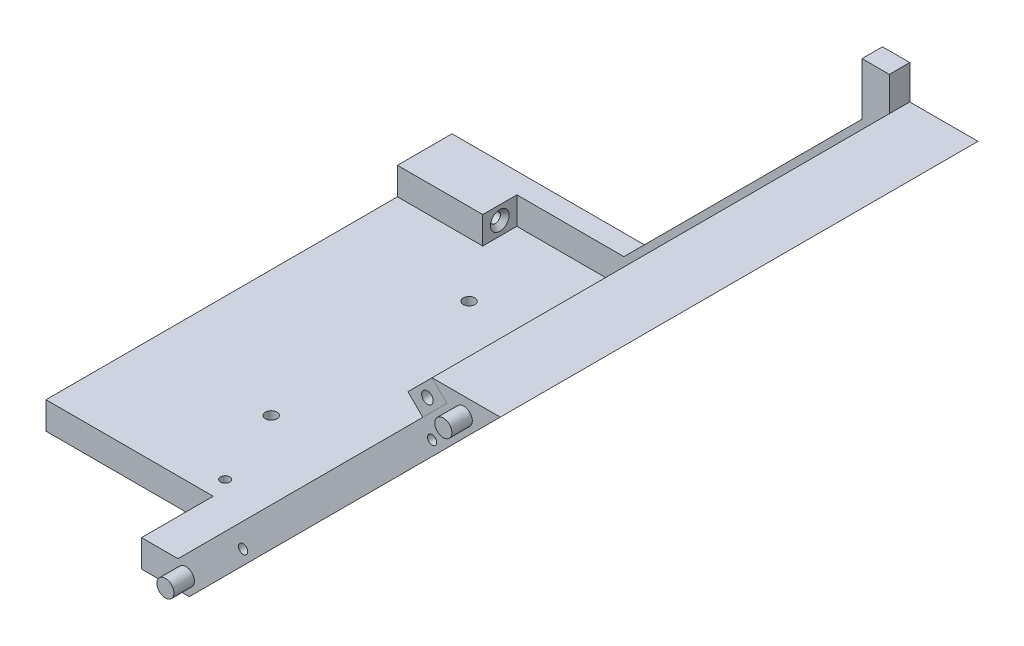
SolidWorks part; units mm, degrees
ref_plane "Plan de face" through (0, 0, 0) normal (0, 0, 1) x (1, 0, 0)
ref_plane "Plan de dessus" through (0, 0, 0) normal (0, 1, 0) x (1, 0, 0)
ref_plane "Plan de droite" through (0, 0, 0) normal (1, 0, 0) x (0, 0, -1)
sketch "Main-Sketch" plane through (0, 0, 0) normal (0, 0, 1) x (1, 0, 0)
  line L0 (0, 0) -> (63, 0)
  line L1 (63, 0) -> (154.15, 91.15)
  line L2 (154.15, 91.15) -> (134.15, 91.15)
  line L3 (134.15, 91.15) -> (138.4931, 86.8069)
  line L4 (138.4931, 86.8069) -> (59.6863, 8)
  line L5 (59.6863, 8) -> (0, 8)
  line L6 (0, 8) -> (0, 0)
  dimension "D1" = 8
  dimension "D2" = 8
  dimension "D3" = 20
  dimension "D4" = 135
  dimension "D5" = 154.15
  dimension "D6" = 63
extrude "Main-Extrusion" add sketch "Main-Sketch" along normal blind 140
sketch "Lcd-Hole-Sketch" plane through (0, 8, 0) normal (0, 1, 0) x (-1, 0, 0)
  line L1 (0, 140) -> (-49, 140)
  line L2 (0, 140) -> (0, 119)
  line L3 (0, 119) -> (-49, 119)
  line L4 (-49, 140) -> (-49, 119)
  dimension "D1" = 21
  dimension "D2" = 49
extrude "Lcd-Hole" cut sketch "Lcd-Hole-Sketch" against normal through all
sketch "Lcd-Fix-Sketch" plane through (0, 8, 0) normal (0, 1, 0) x (1, 0, 0)
  line L1 (49, -119) -> (0, -119) construction
  line L2 (49, -140) -> (49, -119) construction
  circle A0 centre (46.5, -113) radius 1.35
  dimension "D1" = 2.7
  dimension "D2" = 2.5
  dimension "D3" = 6
extrude "Lcd-Fix" cut sketch "Lcd-Fix-Sketch" against normal blind 7
sketch "Bottom-Reinforcement-Sketch" plane through (0, 0, 0) normal (0, 0, 1) x (1, 0, 0)
  line L0 (59.6863, 8) -> (138.4931, 86.8069)
  line L1 (134.15, 101.15) -> (126.15, 101.15)
  line L2 (126.15, 101.15) -> (126.15, 85.7774)
  line L5 (138.4931, 86.8069) -> (59.6863, 8) construction
  line L6 (134.15, 91.15) -> (134.15, 101.15)
  line L7 (59.6863, 8) -> (0, 8)
  line L8 (0, 0) -> (0, 8) construction
  line L9 (0, 8) -> (0, 16)
  line L10 (0, 16) -> (56.3726, 16)
  line L11 (56.3726, 16) -> (126.15, 85.7774)
  line L13 (138.4931, 86.8069) -> (134.15, 91.15)
  dimension "D1" = 8
  dimension "D2" = 10
  dimension "D3" = 8
  dimension "D4" = 8
extrude "Bottom-Reinforcement-Extrusion" add sketch "Bottom-Reinforcement-Sketch" along normal blind 6 separate body
sketch "Power-Board-Hole-Sketch" plane through (22.4244, -40.5756, 188.8128) normal (0.7071, -0.7071, 0) x (0, 0, -1)
  line L1 (150.8128, 154.2882) -> (68.8128, 154.2882)
  line L2 (150.8128, 154.2882) -> (150.8128, 80.3826)
  line L3 (150.8128, 80.3826) -> (68.8128, 80.3826)
  line L4 (68.8128, 154.2882) -> (68.8128, 80.3826)
  line L6 (188.8128, 57.3826) -> (188.8128, 186.2882) construction
  line L7 (48.8128, 57.3826) -> (48.8128, 186.2882) construction
  line L8 (48.8128, 57.3826) -> (188.8128, 57.3826) construction
  line L9 (48.8128, 186.2882) -> (188.8128, 186.2882) construction
  dimension "D1" = 20
  dimension "D2" = 38
  dimension "D3" = 32
  dimension "D4" = 23
extrude "Power-Board-Hole" cut sketch "Power-Board-Hole-Sketch" against normal through all
sketch "Power-Board-Window-Sketch" plane through (22.4244, -40.5756, 188.8128) normal (0.7071, -0.7071, 0) x (0, 0, -1)
  line L0 (150.8128, 80.3826) -> (150.8128, 154.2882) construction
  line L1 (156.8128, 160.2882) -> (62.8128, 160.2882)
  line L2 (156.8128, 160.2882) -> (156.8128, 74.3826)
  line L3 (156.8128, 74.3826) -> (62.8128, 74.3826)
  line L4 (62.8128, 160.2882) -> (62.8128, 74.3826)
  line L5 (150.8128, 154.2882) -> (68.8128, 154.2882) construction
  line L6 (68.8128, 154.2882) -> (68.8128, 80.3826) construction
  line L7 (68.8128, 80.3826) -> (150.8128, 80.3826) construction
  dimension "D1" = 6
  dimension "D2" = 6
  dimension "D3" = 6
  dimension "D4" = 6
extrude "Power-Board-Window" cut sketch "Power-Board-Window-Sketch" against normal blind 5
sketch " Power-Board-Window-Fix-Sketch" plane through (27.9645, -27.9645, 0) normal (0.7071, -0.7071, 0) x (0, 0, -1)
  line L0 (-38, 67.5477) -> (-38, 141.4533) construction
  line L1 (-38, 141.4533) -> (-120, 141.4533) construction
  line L2 (-120, 67.5477) -> (-38, 67.5477) construction
  line L3 (-120, 141.4533) -> (-120, 67.5477) construction
  circle A0 centre (-123, 104.5005) radius 1.35
  circle A1 centre (-35, 104.5005) radius 1.35
  circle A2 centre (-79, 144.4533) radius 1.35
  circle A3 centre (-79, 64.5477) radius 1.35
  point P11 (-38, 104.5005)
  point P15 (-79, 141.4533)
  point P19 (-79, 67.5477)
  point P22 (-120, 104.5005)
  dimension "D1" = 2.7
  dimension "D2" = 3
  dimension "D3" = 3
  dimension "D4" = 3
  dimension "D5" = 3
extrude "Power-Board-Window-Fix" cut sketch " Power-Board-Window-Fix-Sketch" against normal through all
sketch "PowerBoard-Fix-Sketch" plane through (25.8431, -25.8431, 0) normal (-0.7071, 0.7071, 0) x (0, 0, 1)
  line L0 (140, 159.3112) -> (0, 159.3112) construction
  line L2 (6, 47.8614) -> (6, 159.3112) construction
  circle A0 centre (13, 137.3112) radius 4
  circle A1 centre (11, 68.3112) radius 4
  dimension "D1" = 8
  dimension "D2" = 8
  dimension "D3" = 22
  dimension "D4" = 69
  dimension "D5" = 7
  dimension "D6" = 5
extrude "PowerBoard-Fix-Extrusion" add sketch "PowerBoard-Fix-Sketch" along normal blind 5
sketch "PowerBoard-Fix-Hole-Sketch" plane through (22.3076, -22.3076, 0) normal (-0.7071, 0.7071, 0) x (0, 0, 1)
  circle A0 centre (13, 137.3112) radius 1.35
  circle A1 centre (11, 68.3112) radius 1.35
  dimension "D1" = 2.7
extrude "PowerBoard-Fix-Hole" cut sketch "PowerBoard-Fix-Hole-Sketch" against normal through all
sketch "Top-Fix-Sketch" plane through (0, 0, 140) normal (0, 0, 1) x (1, 0, 0)
  line L0 (63, 0) -> (154.15, 91.15) construction
  line L1 (49, 0) -> (49, 8) construction
  line L2 (134.15, 91.15) -> (138.4931, 86.8069) construction
  circle A0 centre (62, 4.6569) radius 2.5
  circle A1 centre (143.4462, 86.0965) radius 2.5
  point P12 (49, 4)
  dimension "D1" = 5
  dimension "D2" = 5
  dimension "D4" = 4
  dimension "D5" = 3.9954
  dimension "D6" = 13
  dimension "D7" = 3
extrude "Top-Fix" add sketch "Top-Fix-Sketch" along normal blind 6
sketch "Top-Fix-Hole-Sketch" plane through (0, 0, 140) normal (0, 0, 1) x (1, 0, 0)
  line L0 (63, 0) -> (154.15, 91.15) construction
  circle A0 centre (78.7574, 20) radius 1.35
  circle A1 centre (134.15, 75.3926) radius 1.35
  dimension "D1" = 2.7
  dimension "D2" = 2.7
  dimension "D3" = 3
  dimension "D4" = 3
  dimension "D5" = 20
  dimension "D6" = 20
extrude "Top-Fix-Hole" cut sketch "Top-Fix-Hole-Sketch" against normal blind 30
sketch "Esquisse3" plane through (0, 0, 140) normal (0, 0, 1) x (1, 0, 0)
  line L0 (138.4931, 86.8069) -> (134.15, 91.15)
  line L1 (134.15, 91.15) -> (127.0789, 84.0789)
  line L2 (127.0789, 84.0789) -> (131.4221, 79.7358)
  line L3 (138.4931, 86.8069) -> (59.6863, 8) construction
  line L4 (131.4221, 79.7358) -> (138.4931, 86.8069)
  dimension "D1" = 10
extrude "Boss.-Extru.2" add sketch "Esquisse3" against normal blind 10 separate body
hole_wizard "Fraisage pour vis à tête fraisée M31" positions "Esquisse5" profile "Esquisse4" countersink size "M3" standard "Ansi Metric" end condition up to next
sketch "Esquisse5" plane through (0, 0, 130) normal (0, 0, -1) x (-1, 0, 0)
  line L0 (-127.0789, 84.0789) -> (-131.4221, 79.7358) construction
  line L1 (-134.15, 91.15) -> (-127.0789, 84.0789) construction
  point P0 (-132.7853, 85.4436)
  dimension "D1" = 5
  dimension "D2" = 3.07
sketch "Esquisse4" plane through (132.7853, 85.4436, 130) normal (1, 0, 0) x (0, 1, 0)
  line L0 (0, 0) -> (0, 10.001)
  line L1 (0, 10.001) -> (1.7, 10.001)
  line L2 (1.7, 10.001) -> (1.7, 1.3)
  line L3 (1.7, 1.3) -> (3, 0)
  line L5 (3, 0) -> (0, 0)
  line L6 (-1.7, 1.3) -> (-3, 0) construction
  line L11 (0, -6.35) -> (0, 107.95) construction
  dimension "Diamètre du perçage jusqu'au prochain" = 3.4
  dimension "Profondeur du perçage jusqu'au prochain" = 10.001
  dimension "Diamètre du fraisage entrant" = 6
  dimension "Angle du fraisage entrant" = 90
sketch "Fix-Sketch" plane through (0, 0, 0) normal (-1, 0, 0) x (0, 0, 1)
  line L0 (119, 0) -> (119, 8) construction
  circle A0 centre (104, 4) radius 2.5
  circle A1 centre (74, 4) radius 2.5
  circle A2 centre (44, 4) radius 2.5
  circle A3 centre (14, 4) radius 2.5
  point P10 (119, 4)
  dimension "D2" = 5
  dimension "D1" = 15
  dimension "D3" = 30
  dimension "D4" = 30
  dimension "D5" = 30
extrude "Fix-Hole" cut sketch "Fix-Sketch" against normal blind 10
ref_plane "EndOfFix-Plan" through (15, 0, 0) normal (-1, 0, 0) x (0, 0, 1)
ref_axis "EndOfFix-Axe" through (15, -0.4, 6) along (0, 1, 0)
ref_plane "EndOFix-Inclined-Plan" through (15.4952, 0, 4.1519) normal (-0.9659, 0, -0.2588) x (0, 1, 0)
sketch "Bottom-Fix-Sketch" plane through (0, 0, 0) normal (-1, 0, 0) x (0, 0, 1)
  line L0 (0, 12.5) -> (6, 11.5)
  line L1 (6, 16) -> (6, 8) construction
  line L2 (6, 11.5) -> (6, 3.5)
  line L3 (6, 3.5) -> (0, 2.5)
  line L4 (0, 8) -> (0, 0) construction
  line L5 (0, 2.5) -> (0, 12.5)
  line L8 (0, 16) -> (0, 8) construction
  point P12 (6, 7.5)
  point P13 (0, 7.5)
  dimension "D1" = 2.5
  dimension "D2" = 8
  dimension "D3" = 10
  dimension "D4" = 3.5
extrude "Bottom-Fix-Extrusion" cut sketch "Bottom-Fix-Sketch" against normal up to surface (16.6077 mm away) up to plane "EndOFix-Inclined-Plan"
sketch "Bottom-Fix-Reinforcement-Sketch" plane through (0, 8, 0) normal (0, 1, 0) x (1, 0, 0)
  line L0 (15, -6) -> (59.6863, -6) construction
  line L1 (0, -16) -> (25, -16)
  line L2 (0, -16) -> (0, -6)
  line L3 (0, -6) -> (25, -6)
  line L4 (25, -16) -> (25, -6)
  line L5 (0, -119) -> (0, -6) construction
  dimension "D1" = 25
  dimension "D2" = 10
extrude "Bottom-Fix-Reinforcement-Extrusion" add sketch "Bottom-Fix-Reinforcement-Sketch" along normal up to surface (8 mm away) up to face at (28.1863, 16, 3)
hole_wizard "Fraisage pour vis à tête fraisée M2.51" positions "Esquisse10" profile "Esquisse9" countersink size "M2.5" standard "Ansi Metric" end condition through all
sketch "Esquisse10" plane through (25, 0, 0) normal (1, 0, 0) x (0, 0, -1)
  line L0 (-16, 16) -> (-16, 8) construction
  line L2 (-6, 16) -> (-16, 16) construction
  point P0 (-11, 12)
  point P4 (-16, 12)
  point P10 (-11, 16)
sketch "Esquisse9" plane through (25, 12, 11) normal (0, 1, 0) x (0, 0, -1)
  line L0 (0, 0) -> (0, 25)
  line L1 (0, 25) -> (1.45, 25)
  line L2 (1.45, 25) -> (1.45, 1.3)
  line L3 (1.45, 1.3) -> (2.75, 0)
  line L5 (2.75, 0) -> (0, 0)
  line L6 (-1.45, 1.3) -> (-2.75, 0) construction
  line L11 (0, -6.35) -> (0, 107.95) construction
  dimension "Diamètre du perçage jusqu'au prochain" = 2.9
  dimension "Profondeur du perçage jusqu'au prochain" = 25
  dimension "Diamètre du fraisage entrant" = 5.5
  dimension "Angle du fraisage entrant" = 90
hole_wizard "Fraisage pour vis à tête fraisée M32" positions "Esquisse11" profile "Esquisse12" countersink size "M3" standard "Ansi Metric" end condition through all
sketch "Esquisse11" plane through (0, 0, 0) normal (0, -1, 0) x (-1, 0, 0)
  line L0 (-49, -140) -> (-63, -140) construction
  line L1 (0, -119) -> (0, 0) construction
  point P1 (-37, -90)
  point P4 (0, 0)
  dimension "D1" = 50
  dimension "D2" = 37
sketch "Esquisse12" plane through (37, 0, 90) normal (1, 0, 0) x (0, 0, -1)
  line L0 (0, 0) -> (0, 101.15)
  line L1 (0, 101.15) -> (1.7, 101.15)
  line L2 (1.7, 101.15) -> (1.7, 1.45)
  line L3 (1.7, 1.45) -> (3.15, 0)
  line L5 (3.15, 0) -> (0, 0)
  line L6 (-1.7, 1.45) -> (-3.15, 0) construction
  line L11 (0, -6.35) -> (0, 107.95) construction
  dimension "Diamètre du perçage jusqu'au prochain" = 3.4
  dimension "Profondeur du perçage jusqu'au prochain" = 101.15
  dimension "Diamètre du fraisage entrant" = 6.3
  dimension "Angle du fraisage entrant" = 90
pattern_linear "HDD-Fix-Linear-Repeat" count 2 spacing 58 along (0, 0, -1) of "Fraisage pour vis à tête fraisée M32"
